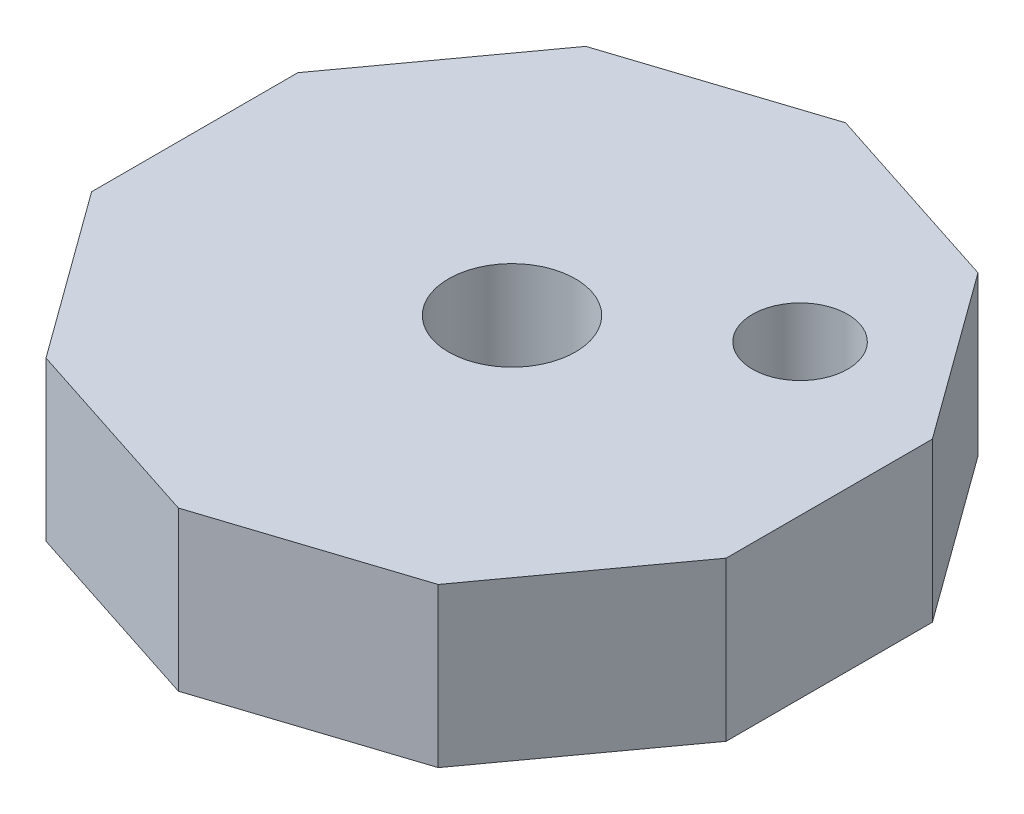
SolidWorks part; units mm, degrees
ref_plane "Front Plane" through (0, 0, 0) normal (0, 0, 1) x (1, 0, 0)
ref_plane "Top Plane" through (0, 0, 0) normal (0, 1, 0) x (1, 0, 0)
ref_plane "Right Plane" through (0, 0, 0) normal (1, 0, 0) x (0, 0, -1)
sketch "Sketch1" plane through (0, 0, 0) normal (0, 1, 0) x (1, 0, 0)
  line L0 (6.1803, -8.5065) -> (10, -3.2492)
  line L1 (0, 10.5146) -> (-6.1803, 8.5065)
  line L2 (-6.1803, 8.5065) -> (-10, 3.2492)
  line L3 (-10, 3.2492) -> (-10, -3.2492)
  line L4 (-10, -3.2492) -> (-6.1803, -8.5065)
  line L5 (-6.1803, -8.5065) -> (0, -10.5146)
  line L6 (0, -10.5146) -> (6.1803, -8.5065)
  line L7 (10, -3.2492) -> (10, 3.2492)
  line L8 (10, 3.2492) -> (6.1803, 8.5065)
  line L9 (6.1803, 8.5065) -> (0, 10.5146)
  circle A0 centre (0, 0) radius 10 construction
  dimension "D1" = 20
extrude "Boss-Extrude1" add sketch "Sketch1" along normal blind 5
sketch "Sketch2" plane through (0, 5, 0) normal (0, 1, 0) x (1, 0, 0)
  line L0 (8.0902, 5.8779) -> (0, 0) construction
  line L1 (10, 3.2492) -> (6.1803, 8.5065) construction
  circle A0 centre (0, 0) radius 2
  circle A1 centre (5.2586, 3.8206) radius 1.5
  dimension "D1" = 4
  dimension "D2" = 3
  dimension "D3" = 3.5
extrude "Cut-Extrude1" cut sketch "Sketch2" against normal blind 5 contours A1 L0 | L0 A1 | A0 region at (5.6328, 5, -3.3056) region at (4.8844, 5, -4.3356)
